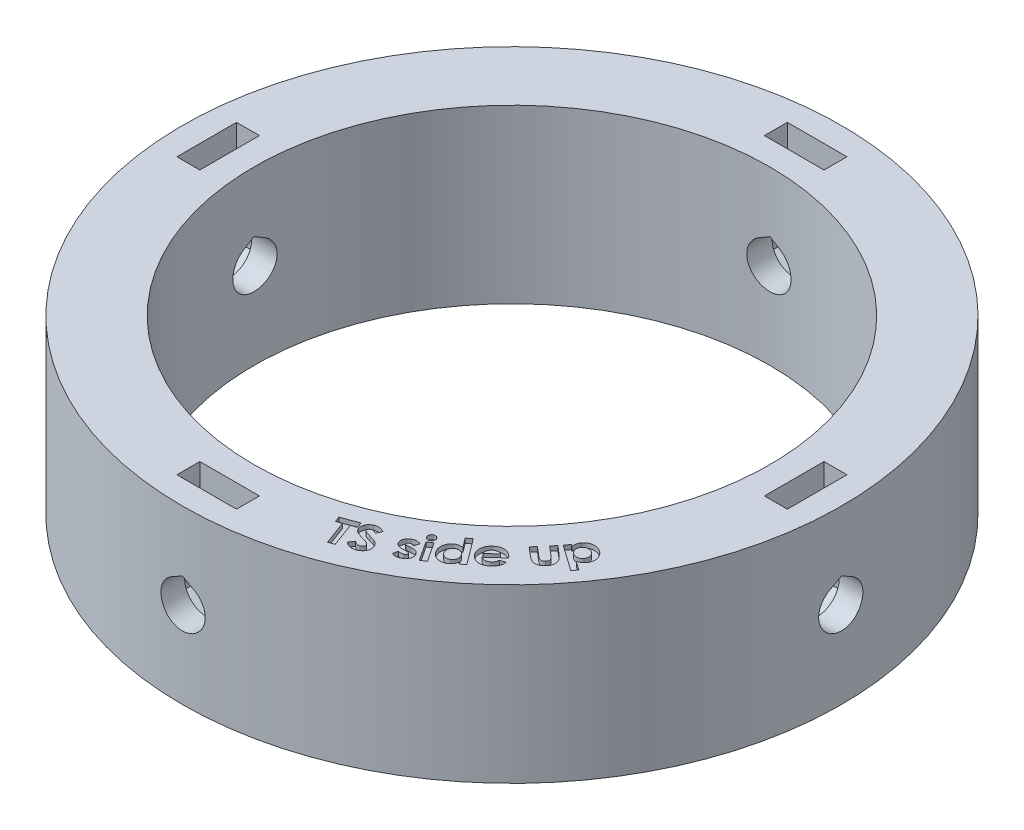
SolidWorks part; units mm, degrees
ref_plane "Front Plane" through (0, 0, 0) normal (0, 0, 1) x (1, 0, 0)
ref_plane "Top Plane" through (0, 0, 0) normal (0, 1, 0) x (1, 0, 0)
ref_plane "Right Plane" through (0, 0, 0) normal (1, 0, 0) x (0, 0, -1)
sketch "Sketch1" plane through (0, 0, 0) normal (0, 1, 0) x (1, 0, 0)
  circle A0 centre (0, 0) radius 36.5125
  circle A1 centre (0, 0) radius 28.575
  dimension "D1" = 73.025
  dimension "D2" = 7.9375
extrude "Boss-Extrude1" add sketch "Sketch1" along normal blind 19.05
sketch "Sketch2" plane through (0, 0, 0) normal (0, 1, 0) x (1, 0, 0)
  line L0 (0, 36.5125) -> (0, 28.575) construction
  line L1 (0, 32.5438) -> (0, 0) construction
  circle A0 centre (0, 0) radius 36.5125 construction
  circle A1 centre (0, 0) radius 28.575 construction
  dimension "D1" = 32.5438
ref_plane "Plane1" through (0, 0, -32.5438) normal (0, 0, 1) x (1, 0, 0)
sketch "Sketch3" plane through (0, 0, -32.5438) normal (0, 0, 1) x (1, 0, 0)
  line L0 (0, 0) -> (0, 9.525) construction
  line L1 (0, 11.9761) -> (0, 12.3553) construction
  line L2 (0, 12.3553) -> (-1.2256, 11.6477)
  line L3 (0, 12.3553) -> (1.2256, 11.6477)
  circle A0 centre (0, 9.525) radius 2.4511
  dimension "D1" = 4.9022
  dimension "D2" = 9.525
  dimension "D3" = 60
extrude "Cut-Extrude1" cut sketch "Sketch3" against normal blind 5.08 and the other way blind 5.08 contours A0 L3 L2 | A0 region at (0, 12.0584, -32.5438) region at (0, 9.525, -32.5438)
sketch "Sketch4" plane through (0, 0, -32.5438) normal (0, 0, 1) x (1, 0, 0)
  line L0 (0, 0) -> (0, 9.525) construction
  line L1 (-3.302, 13.9977) -> (-3.302, 26.0916)
  line L2 (0, 5.7122) -> (3.302, 7.6186)
  line L3 (3.302, 7.6186) -> (3.302, 14.3655)
  line L6 (-3.302, 13.9977) -> (-3.302, 7.6186)
  line L7 (-3.302, 7.6186) -> (0, 5.7122)
  line L8 (-3.302, 26.0916) -> (3.302, 26.0916)
  line L9 (3.302, 26.0916) -> (3.302, 14.3655)
  line L11 (6.3778, 9.6556) -> (0.8533, 12.8452) [skipped]
  line L12 (3.0758, 15.1136) -> (-2.4487, 11.9241) [skipped]
  circle A0 centre (0, 9.525) radius 3.302 construction
  dimension "D1" = 6.604
  dimension "D2" = 12.0939
  dimension "D3" = 6.3791
  dimension "D4" = 9.525
extrude "Cut-Extrude2" cut sketch "Sketch4" against normal blind 1.27 and the other way blind 1.27
sketch "Sketch5" plane through (0, 0, 0) normal (0, 0, 1) x (1, 0, 0)
  line L0 (0, -8.9681) -> (0, 44.1563) construction
pattern_circular "CirPattern1" count 4 over 360 about axis through (0, -8.9681, 0) along (0, 1, 0) of "Cut-Extrude1", "Cut-Extrude2" reverse direction yes
sketch "Sketch7" plane through (0, 19.05, 0) normal (0, 1, 0) x (1, 0, 0)
  arc A0 (10.8843, -32.1817) -> (30.0268, -15.891) centre (0, 0) ccw
  circle A1 centre (0, 0) radius 36.5125 construction
  text T0 "<b>TS side up</b>"
  dimension "D1" = 2.54
sketch "Sketch8" plane through (0, 19.05, 0) normal (0, 1, 0) x (1, 0, 0)
  text T0 "<b>TS side up</b>"
extrude "Cut-Extrude3" cut sketch "Sketch8" against normal blind 0.5
